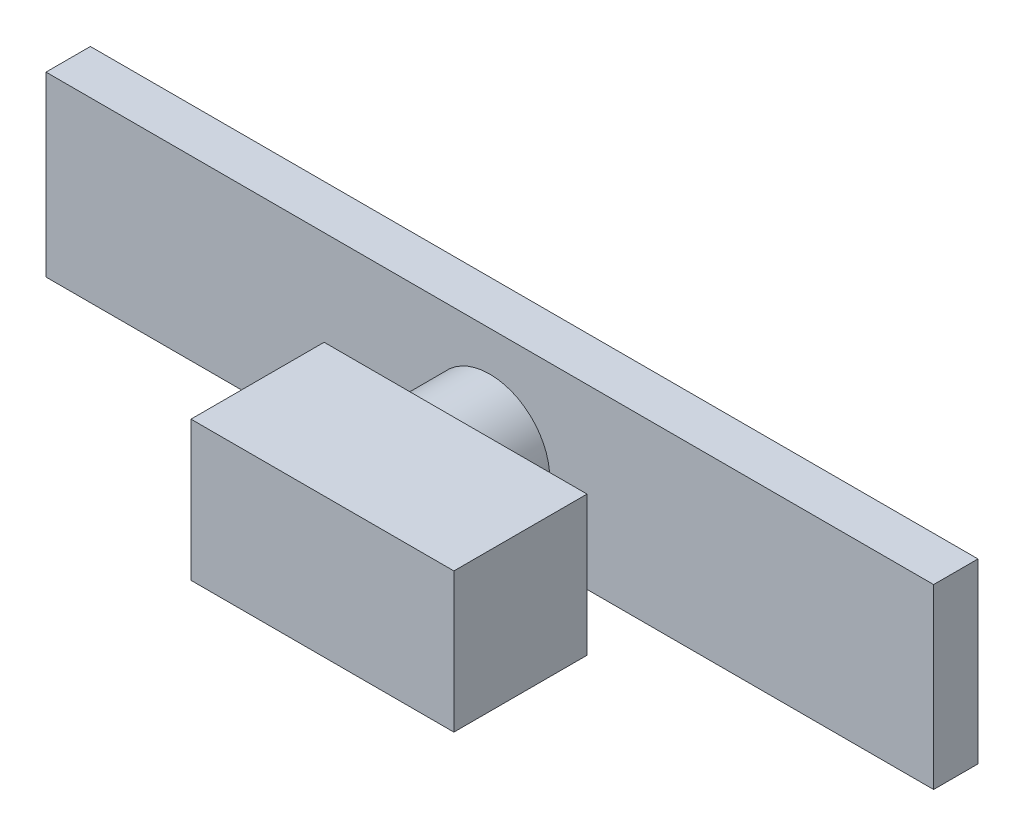
SolidWorks part; units mm, degrees
ref_plane "Front Plane" through (0, 0, 0) normal (0, 0, 1) x (1, 0, 0)
ref_plane "Top Plane" through (0, 0, 0) normal (0, 1, 0) x (1, 0, 0)
ref_plane "Right Plane" through (0, 0, 0) normal (1, 0, 0) x (0, 0, -1)
sketch "Sketch2" plane through (0, 0, 0) normal (0, 0, 1) x (1, 0, 0)
  line L1 (-47.8692, 21.2481) -> (206.1308, 21.2481)
  line L2 (-47.8692, 21.2481) -> (-47.8692, 8.5481)
  line L3 (-47.8692, 8.5481) -> (206.1308, 8.5481)
  line L4 (206.1308, 21.2481) -> (206.1308, 8.5481)
  dimension "D1" = 12.7
  dimension "D2" = 254
extrude "Boss-Extrude1" add sketch "Sketch2" along normal blind 50.8
sketch "Sketch3" plane through (0, 21.2481, 0) normal (0, 1, 0) x (1, 0, 0)
  circle A0 centre (79.1308, -28.4831) radius 17.1408
extrude "Boss-Extrude2" add sketch "Sketch3" along normal blind 19.05
sketch "Sketch4" plane through (0, 40.2981, 0) normal (0, 1, 0) x (1, 0, 0)
  line L1 (50.7675, -8.111) -> (126.0034, -8.111)
  line L2 (50.7675, -8.111) -> (50.7675, -48.0661)
  line L3 (50.7675, -48.0661) -> (126.0034, -48.0661)
  line L4 (126.0034, -8.111) -> (126.0034, -48.0661)
extrude "Boss-Extrude3" add sketch "Sketch4" along normal blind 38.1
scale "Scale2" scale about centroid uniform scaling yes scale factor 0.06
move or copy body "Body-Move/Copy1" bodies to move or copy 105 copy no rotation origin (0, 33.6669, 26.5501) rotation axis (1, 0, 0) rotation angle 90
move or copy body "Body-Move/Copy3" bodies to move or copy 106 copy no translate (-50.8, 0, -50.8)
scale "Scale5" scale about centroid uniform scaling yes scale factor 0.25
move or copy body "Body-Move/Copy9" bodies to move or copy 111 copy no translate (-50.8, 0, 0)
move or copy body "Body-Move/Copy13" bodies to move or copy 117 copy no translate (0, -50.8, 0)
scale "Scale6" bodies to scale 121 scale about centroid uniform scaling yes scale factor 0.25
move or copy body "Body-Move/Copy16" bodies to move or copy 122 copy no translate (0, 0, -12.7)
move or copy body "Body-Move/Copy17" bodies to move or copy 125 copy no translate (0, 0, -76.2)
